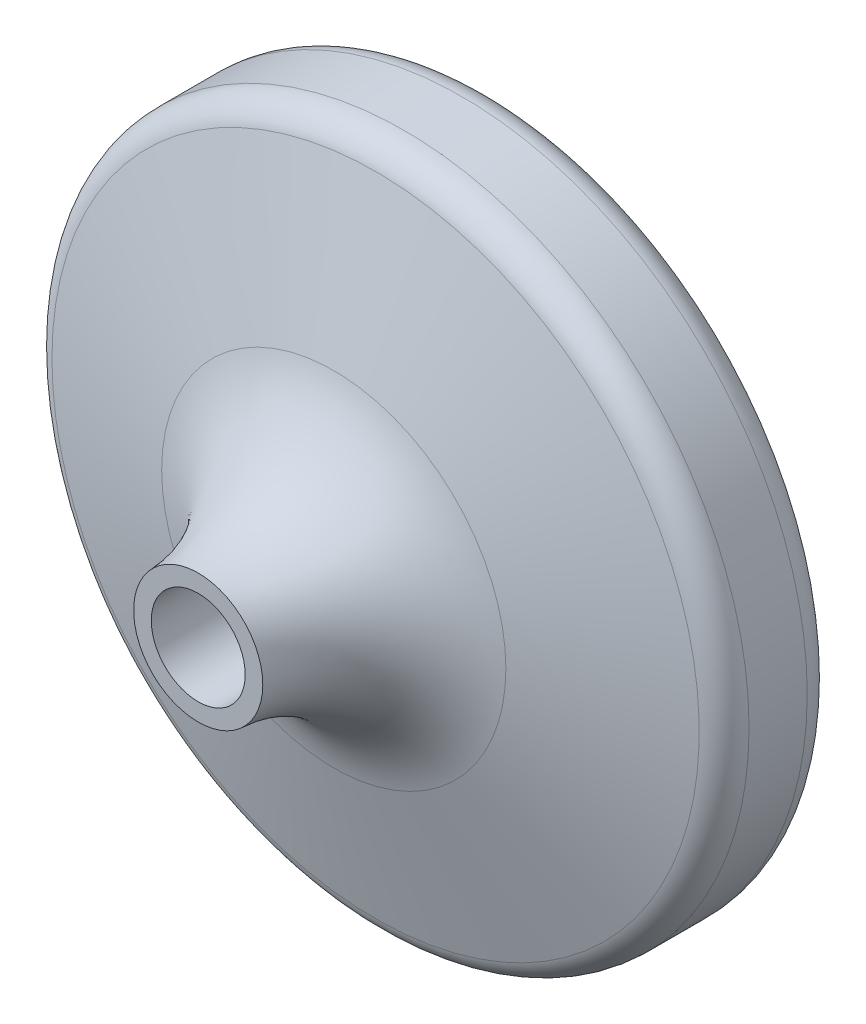
SolidWorks part; units mm, degrees
ref_plane "Front Plane" through (0, 0, 0) normal (0, 0, 1) x (1, 0, 0)
ref_plane "Top Plane" through (0, 0, 0) normal (0, 1, 0) x (1, 0, 0)
ref_plane "Right Plane" through (0, 0, 0) normal (1, 0, 0) x (0, 0, -1)
sketch "Sketch1" plane through (0, 0, 0) normal (0, 0, 1) x (1, 0, 0)
  circle A0 centre (0, 0) radius 8
  circle A1 centre (0, 0) radius 11
  dimension "D1" = 22
  dimension "D2" = 16
extrude "Boss-Extrude1" add sketch "Sketch1" along normal mid plane 80
sketch "Sketch2" plane through (0, 0, 0) normal (1, 0, 0) x (0, 0, -1)
  line L0 (-25, 0) -> (-9.778, 55.1464)
  line L1 (-4.9582, 58.816) -> (4.9582, 58.816)
  line L2 (9.778, 55.1464) -> (25, 0)
  line L3 (25, 0) -> (-25, 0) construction
  line L4 (-25, 0) -> (25, 0)
  arc A1 (-9.778, 55.1464) -> (-4.9582, 58.816) centre (-4.9582, 53.816) cw
  arc A2 (9.778, 55.1464) -> (4.9582, 58.816) centre (4.9582, 53.816) ccw
  point P2 (0, 58.816)
  point P20 (8.765, 58.816)
  dimension "D1" = 50
  dimension "D2" = 5
revolve "Revolve1" add sketch "Sketch2" angle 360 about L3
fillet "Fillet1" radius 25 2 edges at (11, 0, -21.9637) (-11, 0, 21.9637)
